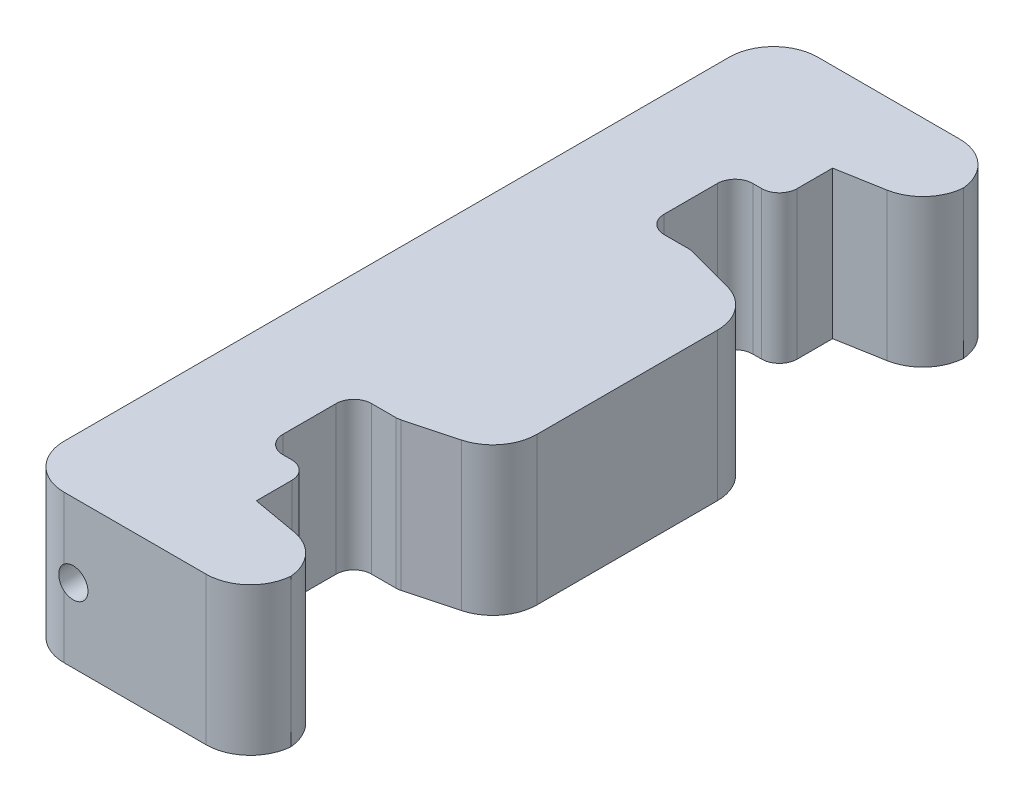
SolidWorks part; units mm, degrees
ref_plane "Front Plane" through (0, 0, 0) normal (0, 0, 1) x (1, 0, 0)
ref_plane "Top Plane" through (0, 0, 0) normal (0, 1, 0) x (1, 0, 0)
ref_plane "Right Plane" through (0, 0, 0) normal (1, 0, 0) x (0, 0, -1)
sketch "Sketch1" plane through (0, 0, 0) normal (0, 1, 0) x (1, 0, 0)
  line L0 (-13.97, 32.385) -> (13.97, -32.385) construction
  line L1 (-13.97, 32.385) -> (13.97, 32.385)
  line L2 (-13.97, 32.385) -> (-13.97, -32.385)
  line L3 (-13.97, -32.385) -> (13.97, -32.385)
  line L4 (13.97, 32.385) -> (13.97, -32.385)
  line L5 (-13.97, -32.385) -> (13.97, 32.385) construction
  line L6 (5.842, 12.573) -> (5.842, -12.573)
  line L7 (13.97, 32.385) -> (5.842, 32.385)
  line L8 (13.97, 32.385) -> (13.97, 12.573)
  line L9 (13.97, 12.573) -> (5.842, 12.573)
  line L10 (5.842, 32.385) -> (5.842, 12.573)
  line L11 (13.97, -32.385) -> (5.842, -32.385)
  line L12 (13.97, -32.385) -> (13.97, -12.573)
  line L13 (13.97, -12.573) -> (5.842, -12.573)
  line L14 (5.842, -32.385) -> (5.842, -12.573)
  line L15 (5.842, 12.573) -> (-1.27, 12.573)
  line L16 (5.842, 12.573) -> (5.842, 24.765)
  line L17 (5.842, 24.765) -> (-1.27, 24.765)
  line L18 (-1.27, 12.573) -> (-1.27, 24.765)
  line L23 (5.842, -12.573) -> (-1.27, -12.573)
  line L24 (5.842, -12.573) -> (5.842, -24.765)
  line L25 (5.842, -24.765) -> (-1.27, -24.765)
  line L26 (-1.27, -12.573) -> (-1.27, -24.765)
  line L28 (-1.27, 12.573) -> (-5.08, 12.573)
  line L29 (-1.27, 12.573) -> (-1.27, 20.193)
  line L30 (-1.27, 20.193) -> (-5.08, 20.193)
  line L31 (-5.08, 12.573) -> (-5.08, 20.193)
  line L32 (-1.27, -12.573) -> (-5.08, -12.573)
  line L33 (-1.27, -12.573) -> (-1.27, -20.193)
  line L34 (-1.27, -20.193) -> (-5.08, -20.193)
  line L35 (-5.08, -12.573) -> (-5.08, -20.193)
  point P4 (0, 0)
  dimension "D1" = 27.94
  dimension "D2" = 64.77
  dimension "D3" = 19.812
  dimension "D4" = 8.128
  dimension "D5" = 19.812
  dimension "D6" = 8.128
  dimension "D7" = 12.7
  dimension "D8" = 7.62
  dimension "D9" = 7.62
  dimension "D10" = 12.7
  dimension "D11" = 7.62
  dimension "D12" = 3.81
  dimension "D13" = 7.62
  dimension "D14" = 3.81
extrude "Boss-Extrude1" add sketch "Sketch1" along normal blind 12.7 contours L35 L32 L23 L6 L15 L28 L31 L30 L18 L17 L10 L1 L2 L3 L14 L25 L26 L34 region at (-5.1601, 0, 0)
sketch "Sketch2" plane through (0, 12.7, 0) normal (0, 1, 0) x (1, 0, 0)
  line L0 (-1.27, 24.765) -> (5.842, 26.019)
  line L1 (5.842, 32.385) -> (5.842, 24.765) construction
  line L2 (5.842, 24.765) -> (-1.27, 24.765) construction
  line L3 (-1.27, -24.765) -> (5.842, -26.019)
  line L4 (5.842, -32.385) -> (5.842, -24.765) construction
  line L5 (5.842, -24.765) -> (-1.27, -24.765) construction
  line L6 (-1.27, -12.573) -> (5.842, -10.6673)
  line L7 (5.842, -12.573) -> (-5.08, -12.573) construction
  line L8 (5.842, 12.573) -> (5.842, -12.573) construction
  line L9 (-1.27, 12.573) -> (5.842, 10.6673)
  line L10 (5.842, 12.573) -> (-5.08, 12.573) construction
  line L11 (-1.27, 24.765) -> (5.842, 24.765)
  line L12 (5.842, 24.765) -> (5.842, 26.019)
  line L13 (-1.27, 12.573) -> (5.842, 12.573)
  line L14 (5.842, 12.573) -> (5.842, 10.6673)
  line L15 (-1.27, -12.573) -> (5.842, -12.573)
  line L16 (5.842, -10.6673) -> (5.842, -12.573)
  line L17 (-1.27, -24.765) -> (5.842, -24.765)
  line L18 (5.842, -24.765) -> (5.842, -26.019)
  dimension "D1" = 10
  dimension "D2" = 10
  dimension "D3" = 15
  dimension "D4" = 15
extrude "Cut-Extrude1" cut sketch "Sketch2" against normal through all
fillet "Fillet4" radius 1.524 8 edges at (-1.27, 6.35, -12.573) (-1.27, 6.35, 12.573) (-1.27, 6.35, 20.193) (-5.08, 6.35, 20.193) (-5.08, 6.35, 12.573) (-5.08, 6.35, -12.573) (-5.08, 6.35, -20.193) (-1.27, 6.35, -20.193)
fillet "Fillet5" radius 3.81 8 edges at (-13.97, 6.35, 32.385) (-13.97, 6.35, -32.385) (5.842, 6.35, -32.385) (5.842, 6.35, -26.019) (5.842, 6.35, -10.6673) (5.842, 6.35, 10.6673) (5.842, 6.35, 32.385) (5.842, 6.35, 26.019)
sketch "Sketch3" plane through (0, 0, 32.385) normal (0, 0, 1) x (1, 0, 0)
  line L0 (-10.16, 0) -> (2.032, 0) construction
  circle A0 centre (-9.392, 6.35) radius 1.27
  dimension "D1" = 2.54
  dimension "D2" = 6.35
extrude "Cut-Extrude2" cut sketch "Sketch3" against normal through all
